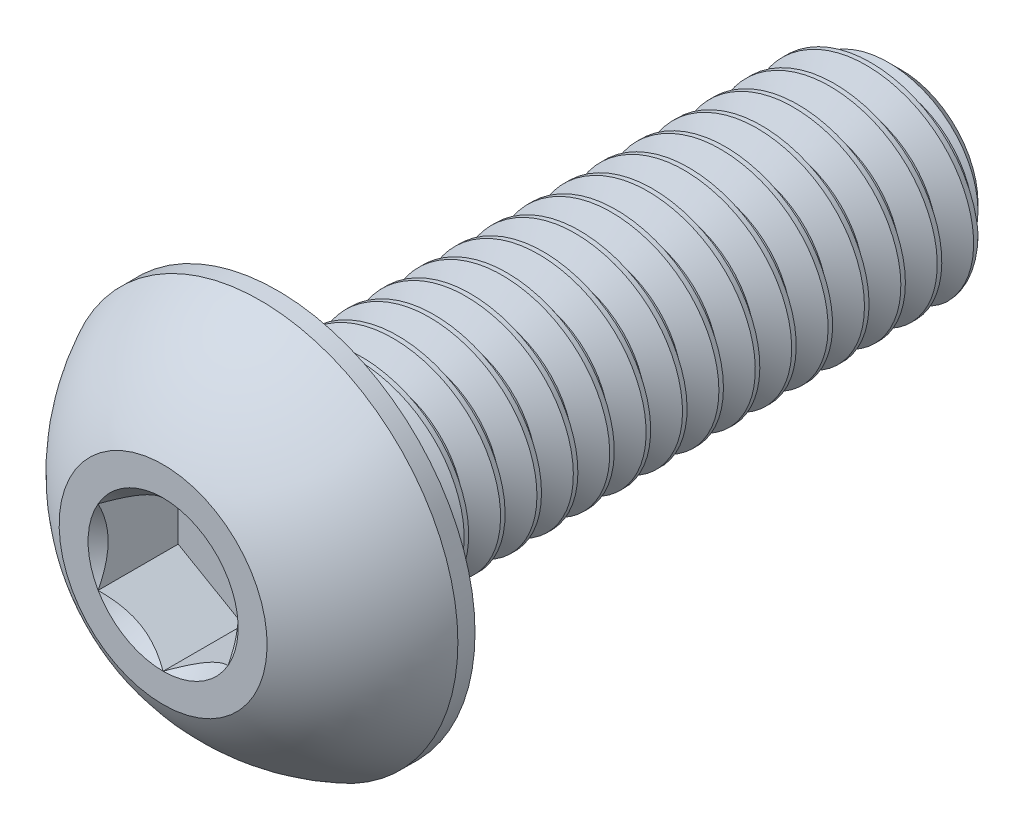
SolidWorks part; units mm, degrees
ref_plane "Front" through (0, 0, 0) normal (0, 0, 1) x (1, 0, 0)
ref_plane "Top" through (0, 0, 0) normal (0, 1, 0) x (1, 0, 0)
ref_plane "Right" through (0, 0, 0) normal (1, 0, 0) x (0, 0, -1)
sketch "Sketch1" plane through (0, 0, 0) normal (1, 0, 0) x (0, 0, -1)
  line L2 (2.2, 2) -> (14.2, 2)
  line L3 (14.2, 2) -> (14.2, 0)
  line L4 (14.2, 0) -> (2.2, 0)
  line L6 (1.87, 3.8) -> (2.2, 3.8) construction
  line L7 (14.2, 2) -> (14.2, -2) construction
  line L8 (0, 0) -> (2.2, 0) construction
  line L9 (2.2, 3.8) -> (2.2, -3.8) construction
  line L11 (2.2, 2) -> (2.2, 0)
  line L13 (0, 1.25) -> (0, -1.25) construction
  line L14 (0, 1.25) -> (0, 2) construction
  line L15 (14.1562, 2.0758) -> (14.5062, 1.4696) construction
  line L16 (14.5062, 1.4696) -> (14.8562, 2.0758) construction
  line L17 (14.8562, 2.0758) -> (14.1562, 2.0758) construction
  line L18 (14.2, 2) -> (14.8125, 2) construction
  line L19 (14.5062, 2.0758) -> (14.5062, 2) construction
  line L20 (14.5062, 2) -> (14.5062, 1.5453) construction
  line L21 (14.5062, 1.5453) -> (14.5062, 1.4696) construction
  line L22 (14.4625, 1.5453) -> (14.55, 1.5453)
  line L23 (14.1781, 2.0379) -> (14.8344, 2.0379)
  line L24 (14.55, 1.5453) -> (14.8344, 2.0379)
  line L25 (14.4625, 1.5453) -> (14.1781, 2.0379)
  line L26 (13.675, 2) -> (14.2, 1.475)
  arc A3 (0, 2) -> (1.87, 3.8) centre (3.7264, 0) cw construction
  point P29 (14.5062, 2.0379)
  point P30 (12.45, -2)
  dimension "D1" = 0.33
  dimension "Pitch" = 0.7
  dimension "D3" = 0.0875
  dimension "D2" = 0.525
  dimension "D4" = 45
  dimension "D5" = 1.75
sketch "Sketch10" plane through (0, 0, 0) normal (1, 0, 0) x (0, 0, -1)
  line L0 (13.675, 2) -> (14.2, 1.475) construction
  line L1 (13.675, 2) -> (14.2, 1.475)
  line L4 (14.2, 2) -> (2.2, 2)
  line L5 (14.2, 0) -> (14.2, 2)
  line L6 (2.2, 0) -> (14.2, 0)
  line L7 (2.2, 2) -> (2.2, 0)
  line L8 (13.675, 2) -> (2.2, 2)
  line L9 (14.2, 0) -> (14.2, 1.475)
  line L10 (2.2, 0) -> (14.2, 0)
  line L11 (2.2, 2) -> (2.2, 0)
  dimension "D1" = 0
revolve "Revolve3" add sketch "Sketch10" angle 360 about L8
sketch "Sketch7" plane through (0, 0, 0) normal (1, 0, 0) x (0, 0, -1)
  line L6 (1.87, 3.8) -> (2.2, 3.8) construction
  line L8 (0, 0) -> (2.2, 0) construction
  line L11 (2.2, 3.8) -> (2.2, -3.8) construction
  line L12 (1.87, 3.8) -> (2.2, 3.8)
  line L13 (0, 0) -> (2.2, 0)
  line L14 (0, 1.25) -> (0, -1.25) construction
  line L15 (2.2, 3.8) -> (2.2, 0)
  line L16 (0, 2) -> (0, 0)
  arc A2 (1.87, 3.8) -> (0, 2) centre (3.7264, 0) ccw construction
  arc A3 (1.87, 3.8) -> (0, 2) centre (3.7264, 0) ccw
revolve "Revolve2" add sketch "Sketch7" angle 360 mid plane about L13
sketch "Sketch5" plane through (0, 0, 0) normal (0, 0, 1) x (1, 0, 0)
  line L1 (1.25, -0.7217) -> (1.25, 0.7217)
  line L2 (1.25, 0.7217) -> (0, 1.4434)
  line L3 (0, 1.4434) -> (-1.25, 0.7217)
  line L4 (-1.25, 0.7217) -> (-1.25, -0.7217)
  line L5 (-1.25, -0.7217) -> (0, -1.4434)
  line L6 (0, -1.4434) -> (1.25, -0.7217)
  circle A0 centre (0, 0) radius 1.25 construction
extrude "Cut-Extrude2" cut sketch "Sketch5" against normal blind 1.54
sketch "Sketch6" plane through (0, 0, 0) normal (0, 0, 1) x (1, 0, 0)
  circle A0 centre (0, 0) radius 1.4434
extrude "Cut-Extrude3" cut sketch "Sketch6" against normal blind 1.54 draft 45
sketch "Sketch9" plane through (0, 0, -2.2) normal (0, 0, -1) x (-1, 0, 0)
  circle A0 centre (0, 0) radius 2 construction
  circle A4 centre (0, 0) radius 2
split "Split1" bodies to split 113 resulting bodies 123 124 split by face at (3.8, 0, -2.2)
sketch "Sketch11" plane through (0, 0, -14.2) normal (0, 0, -1) x (-1, 0, 0)
  circle A0 centre (0, 0) radius 2 construction
  circle A1 centre (0, 0) radius 2
curve "Helix/Spiral1" pitch 0.7 height 14.2 radius 2 centre (0, 0, -14.2) axis (0, 0, 1) start towards (0, 1, 0)
sketch "Sketch12" plane through (0, 0, 0) normal (1, 0, 0) x (0, 0, -1)
  line L0 (14.4625, 1.5453) -> (14.55, 1.5453) construction
  line L1 (14.55, 1.5453) -> (14.8344, 2.0379) construction
  line L2 (14.1781, 2.0379) -> (14.8344, 2.0379) construction
  line L3 (14.4625, 1.5453) -> (14.1781, 2.0379) construction
  line L4 (14.4625, 1.5453) -> (14.55, 1.5453)
  line L5 (14.55, 1.5453) -> (14.8344, 2.0379)
  line L6 (14.1781, 2.0379) -> (14.8344, 2.0379)
  line L7 (14.4625, 1.5453) -> (14.1781, 2.0379)
sweep "Cut-Sweep2" cut profiles "Sketch12" path "Helix/Spiral1" align with end faces yes
extrude "Boss-Extrude1" add sketch "Sketch9" along normal blind 10 draft 45
equation "\"D1@Cut-Extrude2\" = \"Head Ht@Sketch1\" * .7"
equation "\"D1@Sketch1\" = \"Head Ht@Sketch1\" * .15"
equation "\"D1@Cut-Extrude3\" = \"D1@Cut-Extrude2\""
equation "\"D3@Sketch1\" = \"Pitch@Sketch1\" / 8"
equation "\"D2@Sketch1\"=\"Pitch@Sketch1\"*0.75"
equation "\"D3@Helix/Spiral1\" = \"Lg@Sketch1\" + \"Head Ht@Sketch1\""
equation "\"D4@Helix/Spiral1\" = \"Pitch@Sketch1\""
equation "\"D5@Sketch1\"=\"Pitch@Sketch1\"*2.5"
